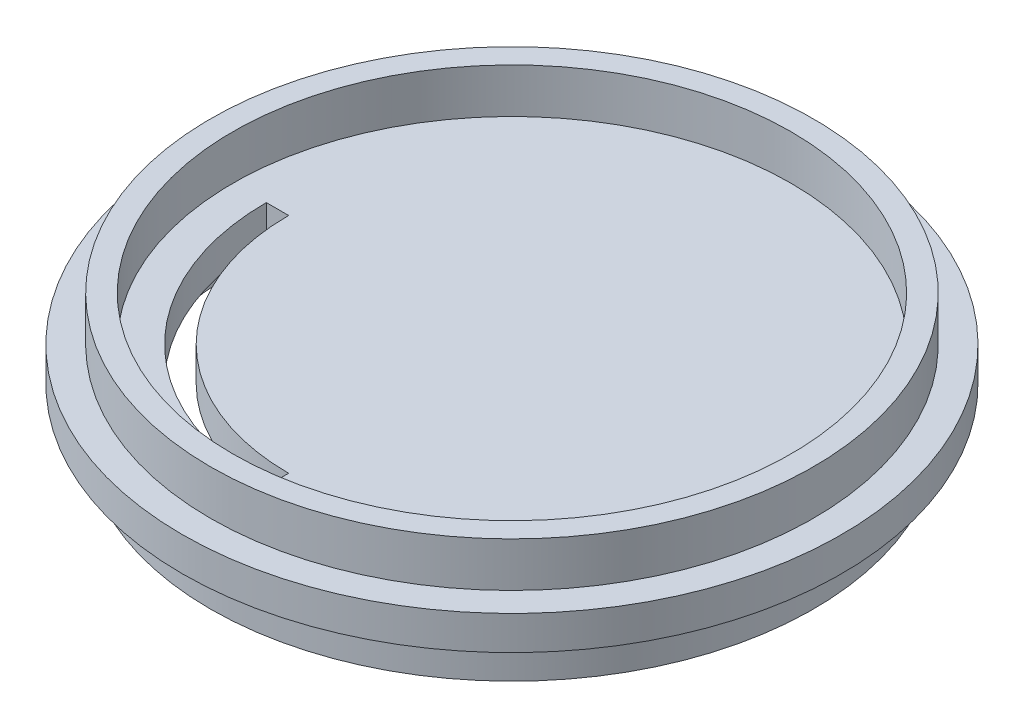
SolidWorks part; units mm, degrees
material "6061-T6 (SS)"
ref_plane "Front Plane" through (0, 0, 0) normal (0, 0, 1) x (1, 0, 0)
ref_plane "Top Plane" through (0, 0, 0) normal (0, 1, 0) x (1, 0, 0)
ref_plane "Right Plane" through (0, 0, 0) normal (1, 0, 0) x (0, 0, -1)
sketch "Sketch1" plane through (0, 0, 0) normal (0, 1, 0) x (1, 0, 0)
  circle A0 centre (0, 0) radius 93.726
  dimension "D1" = 187.452
extrude "Boss-Extrude1" add sketch "Sketch1" along normal mid plane 9.652
sketch "Sketch2" plane through (0, 0, 0) normal (0, 0, 1) x (1, 0, 0)
  line L0 (0, -18.3275) -> (0, 20.8308) construction
  line L1 (0, -4.826) -> (-19.297, -4.826)
  line L2 (-93.726, -4.826) -> (93.726, -4.826) construction
  line L3 (0, -4.826) -> (0, -1.4952)
  line L4 (-0.3818, -1.4952) -> (0, -1.4952)
  arc A0 (-19.297, -4.826) -> (-0.3818, -1.4952) centre (-0.4072, -56.7254) cw
  dimension "D6" = 55.2302
  dimension "D1" = 19.297
  dimension "D2" = 3.3308
  dimension "D3" = 0.3818
revolve "Cut-Revolve1" cut sketch "Sketch2" angle 360 about L0
sketch "Sketch4" plane through (0, 4.826, 0) normal (0, 1, 0) x (1, 0, 0)
  circle A0 centre (0, 0) radius 85.725
  circle A1 centre (0, 0) radius 79.375
  dimension "D1" = 171.45
  dimension "D2" = 158.75
extrude "Boss-Extrude2" add sketch "Sketch4" along normal blind 12.7
ref_plane "Plane1" through (0, 0, -85.725) normal (0, 0, -1) x (-1, 0, 0)
sketch "Sketch5" plane through (0, 0, -85.725) normal (0, 0, -1) x (-1, 0, 0)
  line L0 (0, 19.2786) -> (0, -19.2786) construction
  line L1 (79.375, 17.526) -> (-79.375, 17.526) construction
  circle A0 centre (0, 11.176) radius 1.4351
  dimension "D1" = 2.8702
  dimension "D2" = 6.35
extrude "Cut-Extrude2" [suppressed] cut sketch "Sketch5" against normal blind 12.7
pattern_circular "CirPattern1" [suppressed] count 12 over 360 reverse direction yes of bodies 106
mirror "Mirror2" about plane through (0, 0, 0) normal (0, 1, 0) of "Boss-Extrude2"
sketch "Sketch6" plane through (0, 4.826, 0) normal (0, 1, 0) x (1, 0, 0)
  line L0 (-63.5, 0) -> (-69.85, 0)
  line L1 (0, -69.85) -> (0, -63.5)
  line L2 (0, -19.2786) -> (0, 19.2786) construction
  arc A0 (-69.85, 0) -> (0, -69.85) centre (0, 0) ccw
  arc A1 (-63.5, 0) -> (0, -63.5) centre (0, 0) ccw
  dimension "D1" = 69.85
  dimension "D2" = 63.5
  dimension "D3" = 90
extrude "Cut-Extrude3" cut sketch "Sketch6" against normal up to surface (9.652 mm away) up to face at (0, -4.826, -19.297)
